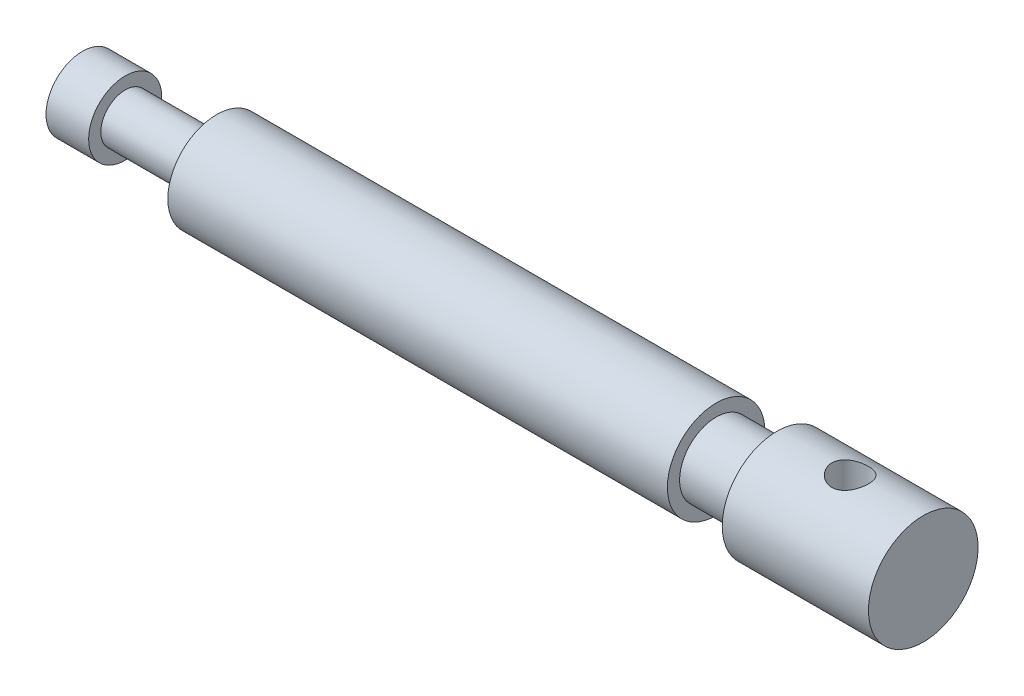
SolidWorks part; units mm, degrees
ref_plane "Front Plane" through (0, 0, 0) normal (0, 0, 1) x (1, 0, 0)
ref_plane "Top Plane" through (0, 0, 0) normal (0, 1, 0) x (1, 0, 0)
ref_plane "Right Plane" through (0, 0, 0) normal (1, 0, 0) x (0, 0, -1)
sketch "Sketch1" plane through (0, 0, 0) normal (0, 0, 1) x (1, 0, 0)
  line L0 (0, 0) -> (349.9946, 0) construction
  line L1 (0, 0) -> (138, 0)
  line L2 (0, 0) -> (7, 0)
  line L3 (0, 0) -> (0, 6)
  line L4 (0, 6) -> (7, 6)
  line L5 (7, 0) -> (7, 6)
  line L6 (7, 0) -> (13, 0)
  line L7 (7, 0) -> (7, 4)
  line L8 (7, 4) -> (13, 4)
  line L9 (13, 0) -> (13, 4)
  line L10 (13, 0) -> (22, 0)
  line L11 (13, 0) -> (13, 4)
  line L12 (13, 4) -> (22, 4)
  line L13 (22, 0) -> (22, 4)
  line L14 (22, 0) -> (104, 0)
  line L15 (22, 0) -> (22, 8)
  line L16 (22, 8) -> (104, 8)
  line L17 (104, 0) -> (104, 8)
  line L18 (104, 0) -> (114, 0)
  line L19 (104, 0) -> (104, 6)
  line L20 (104, 6) -> (114, 6)
  line L21 (114, 0) -> (114, 6)
  line L22 (114, 0) -> (138, 0)
  line L23 (114, 0) -> (114, 9)
  line L24 (114, 9) -> (138, 9)
  line L25 (138, 0) -> (138, 9)
  dimension "D1" = 6
  dimension "D2" = 7
  dimension "D3" = 4
  dimension "D4" = 6
  dimension "D5" = 4
  dimension "D6" = 9
  dimension "D7" = 8
  dimension "D8" = 82
  dimension "D9" = 6
  dimension "D10" = 10
  dimension "D11" = 9
  dimension "D12" = 24
revolve "Revolve1" add sketch "Sketch1" angle 360 about L0 region at (3.5, 3, 0) region at (10, 2, 0) region at (17.5, 2, 0) region at (63, 4, 0) region at (109, 3, 0) region at (126, 4.5, 0)
sketch "Sketch2" plane through (0, 0, 0) normal (0, 1, 0) x (1, 0, 0)
  line L0 (114, 0) -> (126, 0) construction
  line L1 (114, 6) -> (114, -6) construction
  circle A0 centre (126, 0) radius 3
  dimension "D2" = 6
  dimension "D1" = 12
extrude "Cut-Extrude3" cut sketch "Sketch2" against normal blind 10 and the other way blind 10
